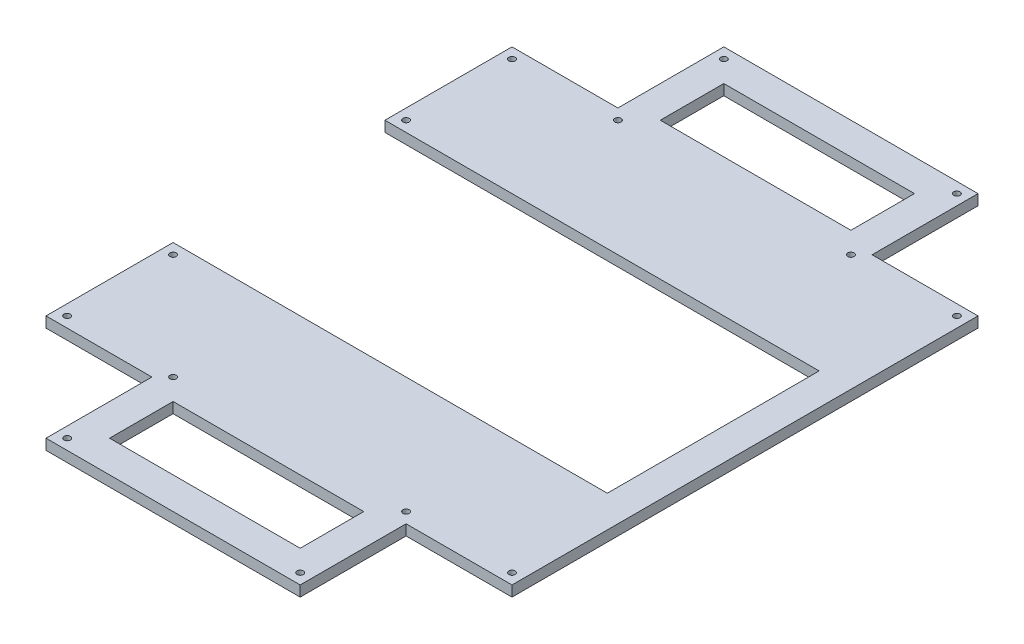
SolidWorks part; units mm, degrees
ref_plane "Plan de face" through (0, 0, 0) normal (0, 0, 1) x (1, 0, 0)
ref_plane "Plan de dessus" through (0, 0, 0) normal (0, 1, 0) x (1, 0, 0)
ref_plane "Plan de droite" through (0, 0, 0) normal (1, 0, 0) x (0, 0, -1)
sketch "Esquisse1" plane through (0, 0, 0) normal (0, 1, 0) x (1, 0, 0)
  line L0 (-60, 110) -> (-60, 160)
  line L1 (110, -110) -> (60, -110)
  line L2 (110, -110) -> (110, 110)
  line L3 (110, 110) -> (60, 110)
  line L4 (-110, -110) -> (-110, -50)
  line L5 (110, -110) -> (-110, 110) construction
  line L6 (110, 110) -> (-110, -110) construction
  line L7 (-60, 160) -> (60, 160)
  line L8 (60, 160) -> (60, 110)
  line L9 (0, 160) -> (0, -89.8749) construction
  line L10 (-108.9276, 0) -> (110, 0) construction
  line L11 (-105, -105) -> (-105, -50) construction
  line L12 (-55, -105) -> (-55, -160) construction
  line L13 (-60, 110) -> (-110, 110)
  line L14 (60, -160) -> (60, -110)
  line L15 (-60, -160) -> (60, -160)
  line L16 (-60, -110) -> (-60, -160)
  line L17 (-60, -110) -> (-110, -110)
  line L18 (45, -145) -> (-45, -145)
  line L19 (45, 115) -> (-45, 115)
  line L20 (45, 115) -> (45, 145)
  line L21 (45, 145) -> (-45, 145)
  line L22 (-45, 115) -> (-45, 145)
  line L23 (45, 115) -> (-45, 145) construction
  line L24 (45, 145) -> (-45, 115) construction
  line L25 (-45, -115) -> (-45, -145)
  line L26 (45, -115) -> (-45, -115)
  line L27 (45, -115) -> (45, -145)
  line L28 (-110, 50) -> (-110, 110)
  line L29 (95, -50) -> (-110, -50)
  line L30 (95, -50) -> (95, 50)
  line L31 (95, 50) -> (-110, 50)
  line L33 (-105, -105) -> (105, -105) construction
  line L34 (105, -105) -> (105, 0) construction
  circle A0 centre (-105, -105) radius 1.5
  circle A1 centre (-105, -55) radius 1.5
  circle A2 centre (-55, -105) radius 1.5
  circle A5 centre (-5, -105) radius 1.5 [skipped]
  circle A6 centre (45, -105) radius 1.5 [skipped]
  circle A7 centre (-55, -155) radius 1.5
  circle A8 centre (-55, 155) radius 1.5
  circle A9 centre (-55, 105) radius 1.5
  circle A10 centre (-105, 105) radius 1.5
  circle A11 centre (-105, 55) radius 1.5
  circle A12 centre (55, -155) radius 1.5
  circle A13 centre (55, -105) radius 1.5
  circle A14 centre (105, -105) radius 1.5
  circle A15 centre (105, 105) radius 1.5
  circle A16 centre (55, 105) radius 1.5
  circle A17 centre (55, 155) radius 1.5
  point P0 (0, 0)
  point P23 (0, 130)
  point P28 (-45, 130)
  point P33 (0.5362, 0)
  dimension "D4" = 3
  dimension "D6" = 50
  dimension "D14" = 5
  dimension "D16" = 5
  dimension "D1" = 220
  dimension "D2" = 50
  dimension "D3" = 50
  dimension "D5" = 5
  dimension "D7" = 30
  dimension "D8" = 15
  dimension "D9" = 15
  dimension "D10" = 15
  dimension "D11" = 60
  dimension "D13" = 2
  dimension "D12" = 60
  dimension "D18" = 120
  dimension "D15" = 4
  dimension "D17" = 2
extrude "Boss.-Extru.1" add sketch "Esquisse1" along normal blind 5
